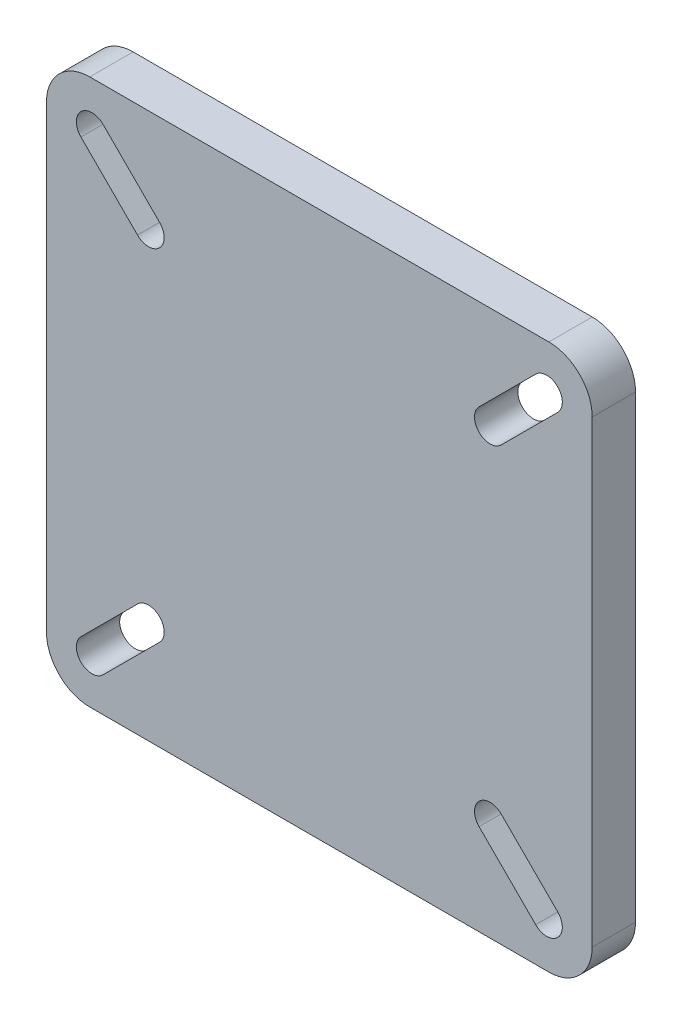
SolidWorks part; units mm, degrees
material "1023 Carbon Steel Sheet (SS)"
ref_plane "Front Plane" through (0, 0, 0) normal (0, 0, 1) x (1, 0, 0)
ref_plane "Top Plane" through (0, 0, 0) normal (0, 1, 0) x (1, 0, 0)
ref_plane "Right Plane" through (0, 0, 0) normal (1, 0, 0) x (0, 0, -1)
sketch "Sketch2" plane through (0, 0, 0) normal (0, 0, 1) x (1, 0, 0)
  line L1 (-60, -60) -> (60, -60)
  line L2 (-60, -60) -> (-60, 60)
  line L3 (-60, 60) -> (60, 60)
  line L4 (60, -60) -> (60, 60)
  line L5 (-60, -60) -> (60, 60) construction
  line L6 (-60, 60) -> (60, -60) construction
  point P0 (0, 0)
  dimension "D1" = 120
extrude "Boss-Extrude1" add sketch "Sketch2" along normal blind 9.525
sketch "Sketch3" plane through (0, 0, 9.525) normal (0, 0, 1) x (1, 0, 0)
  line L0 (-60, 60) -> (0, 0) construction
  line L1 (-50, 50) -> (-37.55, 37.55) construction
  line L2 (-47.5753, 52.4247) -> (-35.1253, 39.9747)
  line L3 (-52.4247, 47.5753) -> (-39.9747, 35.1253)
  arc A0 (-47.5753, 52.4247) -> (-52.4247, 47.5753) centre (-50, 50) ccw
  arc A1 (-39.9747, 35.1253) -> (-35.1253, 39.9747) centre (-37.55, 37.55) ccw
  point P6 (-43.775, 43.775)
  dimension "D2" = 6.858
  dimension "D1" = 50
  dimension "D3" = 37.55
extrude "Cut-Extrude1" cut sketch "Sketch3" against normal through all both and the other way through all
ref_axis "Axis1" through (0, 0, 0) along (0, 0, 1)
pattern_circular "CirPattern1" count 4 over 360 about axis through (0, 0, 0) along (0, 0, 1) of "Cut-Extrude1"
fillet "Fillet1" radius 9.525 4 edges at (60, -60, 4.7625) (60, 60, 4.7625) (-60, -60, 4.7625) (-60, 60, 4.7625)
